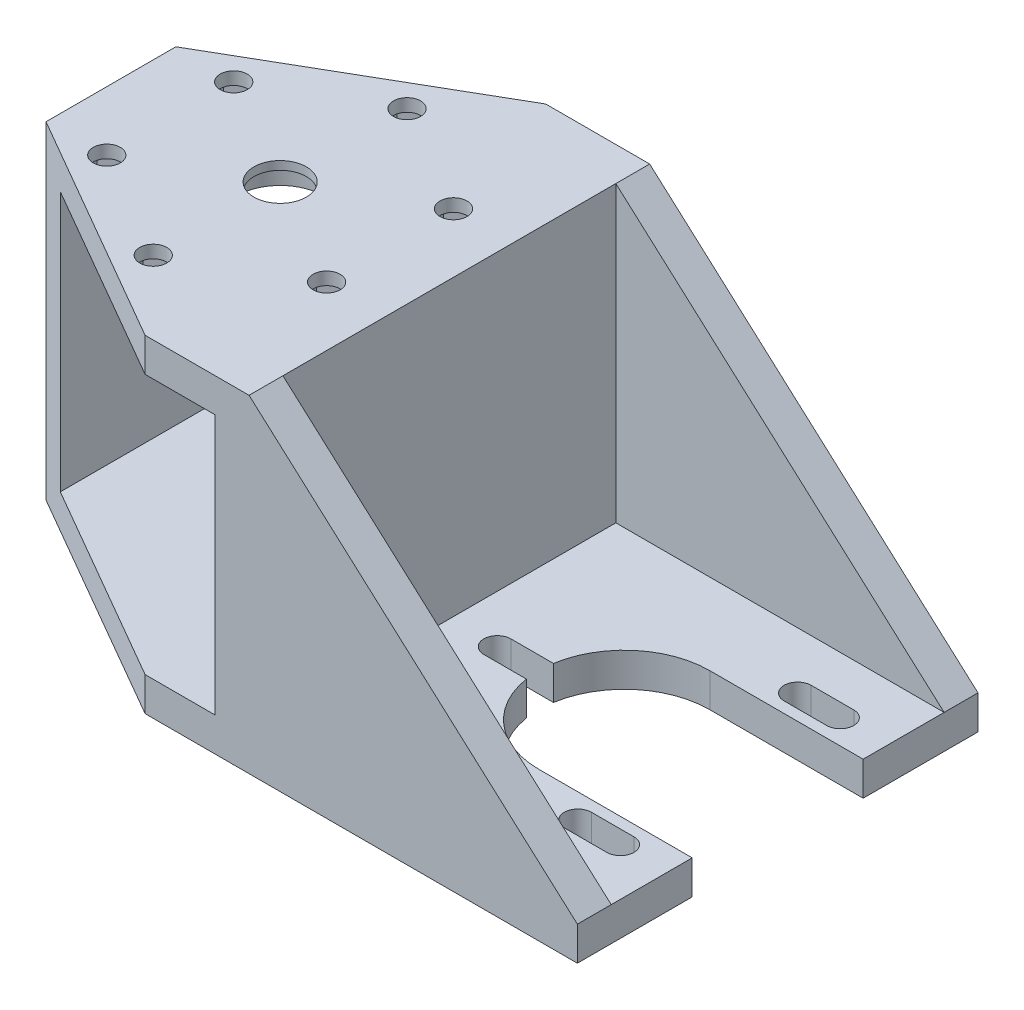
SolidWorks part; units mm, degrees
note: The reader was unsure of these and kept them because the rebuilt part matched: shared geometry of "Sketch3<4>", "Sketch3<5>", "Sketch3<6>".
ref_plane "Front Plane" through (0, 0, 0) normal (0, 0, 1) x (1, 0, 0)
ref_plane "Top Plane" through (0, 0, 0) normal (0, 1, 0) x (1, 0, 0)
ref_plane "Right Plane" through (0, 0, 0) normal (1, 0, 0) x (0, 0, -1)
sketch "Sketch1" plane through (0, 0, 0) normal (0, 0, 1) x (1, 0, 0)
  line L0 (-68.9432, 38.1067) -> (-32.9432, 38.1067)
  line L1 (-32.9432, 38.1067) -> (-32.9432, 3.3767)
  line L2 (-32.9432, 3.3767) -> (8.4068, 3.3767)
  line L3 (8.4068, 3.3767) -> (8.4068, -0.6233)
  line L4 (8.4068, -0.6233) -> (-68.9432, -0.6233)
  line L5 (-68.9432, -0.6233) -> (-68.9432, 3.3767)
  line L6 (-68.9432, 3.3767) -> (-36.9432, 3.3767)
  line L7 (-36.9432, 3.3767) -> (-36.9432, 34.1067)
  line L8 (-36.9432, 34.1067) -> (-68.9432, 34.1067)
  line L9 (-68.9432, 34.1067) -> (-68.9432, 38.1067)
  dimension "D2" = 4
  dimension "D1" = 4
  dimension "D3" = 4
  dimension "D4" = 41.35
  dimension "D5" = 32
  dimension "D6" = 30.73
extrude "Boss-Extrude1" add sketch "Sketch1" along normal blind 39.35
sketch "Sketch3" plane through (0, 3.3767, 0) normal (0, 1, 0) x (1, 0, 0)
  line L0 (-32.9432, -39.35) -> (8.4068, 0)
  line L1 (8.4068, -39.35) -> (8.4068, 0) construction
  line L2 (-36.9432, -39.35) -> (-68.9432, 0)
  line L3 (-12.2682, -19.675) -> (-27.2682, -19.675)
  line L4 (-12.2682, -29.775) -> (8.4068, -29.775)
  line L5 (-12.2682, -29.775) -> (-12.2682, -9.575)
  line L6 (-12.2682, -9.575) -> (8.4068, -9.575)
  line L7 (8.4068, -29.775) -> (8.4068, -9.575)
  line L8 (-60.5747, -21.025) -> (-45.3117, -21.025)
  line L9 (-60.5747, -21.025) -> (-60.5747, -18.325)
  line L10 (-60.5747, -18.325) -> (-45.3117, -18.325)
  line L11 (-45.3117, -21.025) -> (-45.3117, -18.325)
  line L12 (-12.2682, -19.675) -> (-4.7682, -32.6654)
  line L13 (-12.2682, -19.675) -> (-4.7682, -6.6846)
  line L14 (-52.9432, -19.675) -> (-52.9432, -34.675)
  line L15 (-27.2682, -21.275) -> (-22.2406, -21.275)
  line L16 (-27.2682, -21.275) -> (-27.2682, -18.075)
  line L17 (-27.2682, -18.075) -> (-22.2406, -18.075)
  line L18 (-22.2406, -21.275) -> (-22.2406, -18.075)
  line L19 (-4.7682, -34.2654) -> (0.2618, -34.2654)
  line L20 (-4.7682, -34.2654) -> (-4.7682, -31.0654)
  line L21 (-4.7682, -31.0654) -> (0.2618, -31.0654)
  line L22 (0.2618, -34.2654) -> (0.2618, -31.0654)
  line L23 (-4.7682, -5.0846) -> (0.2618, -5.0846)
  line L24 (-4.7682, -5.0846) -> (-4.7682, -8.2846)
  line L25 (-4.7682, -8.2846) -> (0.2618, -8.2846)
  line L26 (0.2618, -5.0846) -> (0.2618, -8.2846)
  line L27 (-52.9432, -19.675) -> (-39.9528, -12.175)
  line L28 (-52.9432, -19.675) -> (-65.9336, -12.175)
  line L29 (-52.9432, -19.675) -> (-52.9432, -4.675)
  line L30 (-52.9432, -19.675) -> (-39.9528, -27.175)
  line L31 (-52.9432, -19.675) -> (-65.9336, -27.175)
  circle A0 centre (-12.2682, -19.675) radius 3.1
  circle A1 centre (-52.9432, -19.675) radius 3.1
  circle A2 centre (-52.9432, -19.675) radius 5.15
  circle A3 centre (-12.2682, -19.675) radius 10.1
  circle A4 centre (-52.9432, -19.675) radius 7.75
  circle A5 centre (-52.9432, -19.675) radius 5.5
  circle A6 centre (-12.2682, -19.675) radius 15
  circle A7 centre (-12.2682, -19.675) radius 14
  circle A8 centre (-4.7682, -32.6654) radius 1.6
  circle A9 centre (-4.7682, -6.6846) radius 1.6
  circle A10 centre (-27.2682, -19.675) radius 1.6
  circle A11 centre (0.2618, -32.6654) radius 1.6
  circle A12 centre (0.2618, -6.6846) radius 1.6
  circle A13 centre (-52.9432, -19.675) radius 15
  circle A14 centre (-52.9432, -34.675) radius 1.6
  circle A15 centre (-65.9336, -27.175) radius 1.6
  circle A16 centre (-65.9336, -12.175) radius 1.6
  circle A17 centre (-52.9432, -4.675) radius 1.6
  circle A18 centre (-39.9528, -12.175) radius 1.6
  circle A19 centre (-39.9528, -27.175) radius 1.6
  point P5 (-12.2682, -29.775)
  point P12 (8.4068, -19.675)
  point P18 (-12.2682, -9.575)
  point P24 (-60.6932, -19.675)
  point P30 (-60.5747, -19.675)
  dimension "D1" = 6.2
  dimension "D2" = 6.2
  dimension "D3" = 10.3
  dimension "D4" = 20.2
  dimension "D6" = 15.5
  dimension "D7" = 11
  dimension "D8" = 28
  dimension "D9" = 30
  dimension "D12" = 3.2
  dimension "D13" = 3.2
  dimension "D14" = 3.2
  dimension "D17" = 30
  dimension "D22" = 3.2
  dimension "D5" = 2.7
  dimension "D10" = 120
  dimension "D11" = 120
  dimension "D15" = 40.675
  dimension "D16" = 5.03
  dimension "D18" = 120
  dimension "D19" = 120
  dimension "D20" = 120
  dimension "D21" = 120
extrude "Cut-Extrude2" cut sketch "Sketch3" against normal blind 3 and the other way offset from surface (33.73 mm away) 3 contours A2 other way up to face at (-52.9432, 34.1067, 19.675)
extrude "Cut-Extrude3" cut sketch "Sketch3<4>" along normal offset from surface (33.73 mm away) 3 contours A5 L8 L11 L10 | A5 L10 L9 L8 up to face at (-58.0932, 34.1067, 19.675) offset beyond the face yes
sketch "Sketch3<4>" plane through (0, 3.3767, 0) normal (0, 1, 0) x (1, 0, 0) same geometry as "Sketch3"
extrude "Cut-Extrude4" cut sketch "Sketch3<5>" against normal through all both and the other way through all contours L4 L7 L6 L5 | A3 | A1 | A8 | L19 L22 L21 L20 | A11 | L23 L26 L25 L24 | A9 | A12 | A10 | L17 L18 L15 L16
sketch "Sketch3<5>" plane through (0, 3.3767, 0) normal (0, 1, 0) x (1, 0, 0) same geometry as "Sketch3"
extrude "Cut-Extrude5" cut sketch "Sketch3<6>" along normal through all contours A14 | A15 | A16 | A17 | A18 | A19
sketch "Sketch3<6>" plane through (0, 3.3767, 0) normal (0, 1, 0) x (1, 0, 0) same geometry as "Sketch3"
sketch "Sketch4" plane through (0, 0, 39.35) normal (0, 0, 1) x (1, 0, 0)
  line L0 (-68.9432, 38.1067) -> (-68.9432, 34.1067)
  line L1 (-68.9432, 38.1067) -> (8.4068, 38.1067)
  line L3 (-68.9432, -0.6233) -> (8.4068, -0.6233)
  line L4 (8.4068, 38.1067) -> (8.4068, -0.6233)
  line L5 (-68.9432, 34.1067) -> (-36.9432, 34.1067)
  line L6 (-36.9432, 34.1067) -> (-36.9432, 3.3767)
  line L7 (-36.9432, 3.3767) -> (-68.9432, 3.3767)
  line L8 (-68.9432, 3.3767) -> (-68.9432, -0.6233)
extrude "Boss-Extrude2" add sketch "Sketch4" along normal blind 4
sketch "Sketch5" plane through (0, 0, 0) normal (0, 0, -1) x (-1, 0, 0)
  line L0 (68.9432, 38.1067) -> (68.9432, 34.1067)
  line L1 (68.9432, 38.1067) -> (-8.4068, 38.1067)
  line L3 (68.9432, -0.6233) -> (-8.4068, -0.6233)
  line L4 (-8.4068, 38.1067) -> (-8.4068, -0.6233)
  line L5 (68.9432, 34.1067) -> (36.9432, 34.1067)
  line L6 (36.9432, 34.1067) -> (36.9432, 3.3767)
  line L7 (36.9432, 3.3767) -> (68.9432, 3.3767)
  line L8 (68.9432, 3.3767) -> (68.9432, -0.6233)
  dimension "D1" = 38.73
extrude "Boss-Extrude3" add sketch "Sketch5" along normal blind 4
sketch "Sketch6" plane through (0, 0, 43.35) normal (0, 0, 1) x (1, 0, 0)
  line L0 (-32.9432, 38.1067) -> (5.8618, 3.3767)
  line L1 (8.4068, 3.3767) -> (-32.9432, 3.3767) construction
  line L2 (5.8618, 3.3767) -> (5.8618, -0.6233)
  line L3 (-68.9432, -0.6233) -> (8.4068, -0.6233) construction
  line L4 (5.8618, -0.6233) -> (8.4068, -0.6233)
  line L5 (8.4068, -0.6233) -> (8.4068, 38.1067)
  line L6 (8.4068, 38.1067) -> (-32.9432, 38.1067)
  line L7 (1.8618, -0.6233) -> (1.8618, 3.3767) construction
  dimension "D1" = 4
extrude "Cut-Extrude6" cut sketch "Sketch6" against normal through all both and the other way through all
sketch "Sketch8" plane through (0, 34.1067, 0) normal (0, -1, 0) x (1, 0, 0)
  line L1 (-65.9336, 15.4082) -> (-68.7336, 13.7916)
  line L2 (-68.7336, 13.7916) -> (-68.7336, 10.5584)
  line L3 (-68.7336, 10.5584) -> (-65.9336, 8.9418)
  line L4 (-65.9336, 8.9418) -> (-63.1336, 10.5584)
  line L5 (-63.1336, 10.5584) -> (-63.1336, 13.7916)
  line L6 (-63.1336, 13.7916) -> (-65.9336, 15.4082)
  line L7 (-65.9336, 30.4082) -> (-68.7336, 28.7916)
  line L8 (-68.7336, 28.7916) -> (-68.7336, 25.5584)
  line L9 (-68.7336, 25.5584) -> (-65.9336, 23.9418)
  line L10 (-65.9336, 23.9418) -> (-63.1336, 25.5584)
  line L11 (-63.1336, 25.5584) -> (-63.1336, 28.7916)
  line L12 (-63.1336, 28.7916) -> (-65.9336, 30.4082)
  line L13 (-52.9432, 1.4418) -> (-50.1432, 3.0584)
  line L14 (-50.1432, 3.0584) -> (-50.1432, 6.2916)
  line L15 (-50.1432, 6.2916) -> (-52.9432, 7.9082)
  line L16 (-52.9432, 7.9082) -> (-55.7432, 6.2916)
  line L17 (-55.7432, 6.2916) -> (-55.7432, 3.0584)
  line L18 (-55.7432, 3.0584) -> (-52.9432, 1.4418)
  line L19 (-39.9528, 8.9418) -> (-37.1528, 10.5584)
  line L20 (-37.1528, 10.5584) -> (-37.1528, 13.7916)
  line L21 (-37.1528, 13.7916) -> (-39.9528, 15.4082)
  line L22 (-39.9528, 15.4082) -> (-42.7528, 13.7916)
  line L23 (-42.7528, 13.7916) -> (-42.7528, 10.5584)
  line L24 (-42.7528, 10.5584) -> (-39.9528, 8.9418)
  line L25 (-39.9528, 23.9418) -> (-37.1528, 25.5584)
  line L26 (-37.1528, 25.5584) -> (-37.1528, 28.7916)
  line L27 (-37.1528, 28.7916) -> (-39.9528, 30.4082)
  line L28 (-39.9528, 30.4082) -> (-42.7528, 28.7916)
  line L29 (-42.7528, 28.7916) -> (-42.7528, 25.5584)
  line L30 (-42.7528, 25.5584) -> (-39.9528, 23.9418)
  line L31 (-52.9432, 37.9082) -> (-55.7432, 36.2916)
  line L32 (-55.7432, 36.2916) -> (-55.7432, 33.0584)
  line L33 (-55.7432, 33.0584) -> (-52.9432, 31.4418)
  line L34 (-52.9432, 31.4418) -> (-50.1432, 33.0584)
  line L35 (-50.1432, 33.0584) -> (-50.1432, 36.2916)
  line L36 (-50.1432, 36.2916) -> (-52.9432, 37.9082)
  circle A0 centre (-65.9336, 12.175) radius 2.8 construction
  circle A1 centre (-65.9336, 27.175) radius 2.8 construction
  circle A2 centre (-52.9432, 4.675) radius 2.8 construction
  circle A3 centre (-39.9528, 12.175) radius 2.8 construction
  circle A4 centre (-39.9528, 27.175) radius 2.8 construction
  circle A5 centre (-52.9432, 34.675) radius 2.8 construction
  dimension "D1" = 5.6
extrude "Cut-Extrude7" cut sketch "Sketch8" against normal offset from surface (2.5 mm away) 1.5 up to face at (-52.9432, 38.1067, 36.275)
sketch "Sketch10" plane through (-68.9432, 0, 0) normal (-1, 0, 0) x (0, 0, 1)
  line L0 (43.35, 38.1067) -> (-4, 38.1067) construction
  line L1 (-4, 38.1067) -> (43.35, 38.1067)
  line L2 (-4, 38.1067) -> (-4, -0.6233)
  line L3 (-4, -0.6233) -> (43.35, -0.6233)
  line L4 (43.35, 38.1067) -> (43.35, -0.6233)
  line L5 (43.35, -0.6233) -> (-4, -0.6233) construction
  line L8 (43.35, 38.1067) -> (43.35, 34.1067) construction
  line L9 (-4, 34.1067) -> (-4, 38.1067) construction
extrude "Boss-Extrude5" add sketch "Sketch10" along normal blind 4
chamfer "Chamfer3" distance 16 angle 60 2 edges at (-72.9432, 18.7417, -4) (-72.9432, 18.7417, 43.35)
equation "\"h_thickness\"=4"
equation "\"D2@Sketch1\"=\"h_thickness\""
equation "\"v_thickness\"=4"
equation "\"D3@Sketch1\"=\"v_thickness\""
equation "\"enc_od\"=38.35"
equation "\"D4@Sketch1\"=\"enc_od\"+3"
equation "\"shaft_clearance\"=32"
equation "\"D5@Sketch1\"=\"shaft_clearance\""
equation "\"D1@Sketch1\"=\"h_thickness\""
equation "\"tok_height\"=17.2"
equation "\"D6@Sketch1\"=\"tok_height\"+\"pin_collar_height\"-2.8+1"
equation "\"D1@Boss-Extrude1\"=\"enc_od\"+1"
equation "\"shaft_dia\"=6.2"
equation "\"D1@Sketch3\"=\"shaft_dia\""
equation "\"D2@Sketch3\"=\"shaft_dia\""
equation "\"bearing_od\"=10.3"
equation "\"D3@Sketch3\"=\"bearing_od\""
equation "\"enc_collar_dia\"=20.9592"
equation "\"tok_pin_od\"=15.5"
equation "\"D6@Sketch3\"=\"tok_pin_od\""
equation "\"tok_pin_id\"=11"
equation "\"D7@Sketch3\"=\"tok_pin_id\""
equation "\"enc_mounting_28\"=28"
equation "\"D8@Sketch3\"=\"enc_mounting_28\""
equation "\"enc_mount_30\"=30"
equation "\"m3_hole\"=3.2"
equation "\"D14@Sketch3\"=\"m3_hole\""
equation "\"D13@Sketch3\"=\"m3_hole\""
equation "\"D12@Sketch3\"=\"m3_hole\""
equation "\"enc_slide\"=5.03"
equation "\"D16@Sketch3\"=\"enc_slide\""
equation "\"pin_collar_height\"= 15.33"
equation "\"D17@Sketch3\"=\"enc_mount_30\""
equation "\"D9@Sketch3\"=\"enc_mount_30\""
equation "\"D22@Sketch3\"=\"m3_hole\""
equation "\"side_wall_thickness\"=4"
equation "\"D1@Boss-Extrude2\"=\"side_wall_thickness\""
equation "\"D1@Boss-Extrude3\"=\"side_wall_thickness\""
equation "\"m3_nut_hole\"=5.6"
equation "\"D1@Sketch8\"=\"m3_nut_hole\""
equation "\"chamfer_dist\"=16"
equation "\"D1@Boss-Extrude5\"=\"side_wall_thickness\""
equation "\"D1@Chamfer3\"=\"chamfer_dist\""
